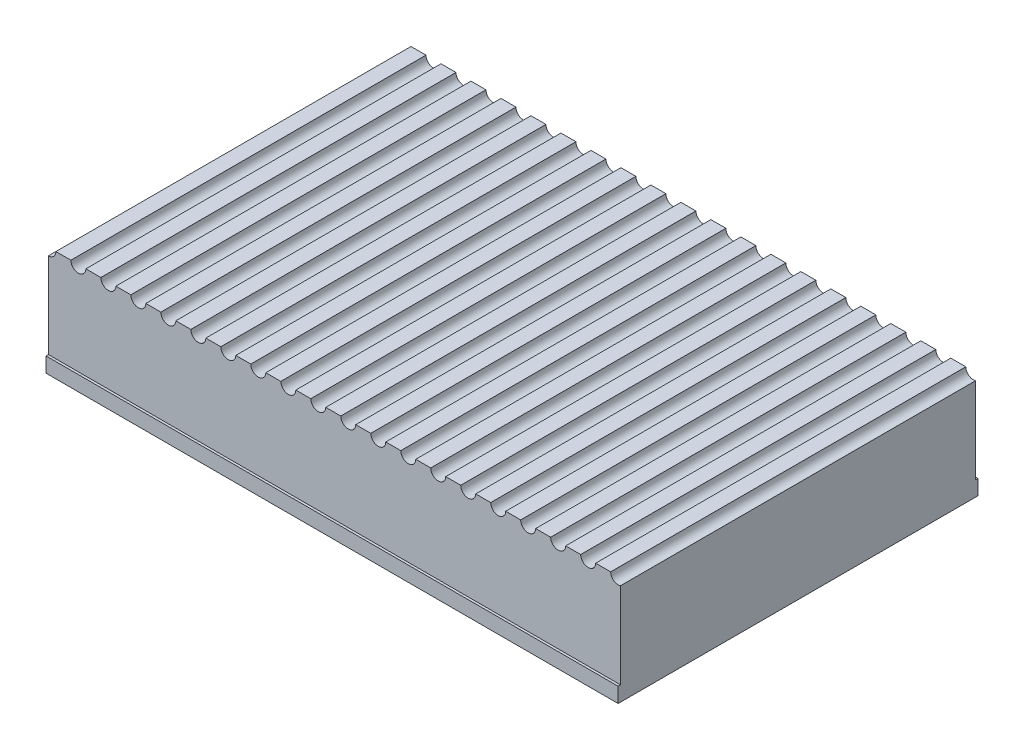
SolidWorks part; units mm, degrees
ref_plane "Front Plane" through (0, 0, 0) normal (0, 0, 1) x (1, 0, 0)
ref_plane "Top Plane" through (0, 0, 0) normal (0, 1, 0) x (1, 0, 0)
ref_plane "Right Plane" through (0, 0, 0) normal (1, 0, 0) x (0, 0, -1)
sketch "Sketch1" plane through (0, 0, 0) normal (0, 1, 0) x (1, 0, 0)
  line L1 (0, 0) -> (-121.1453, 0)
  line L2 (0, 0) -> (0, 76.2)
  line L3 (0, 76.2) -> (-121.1453, 76.2)
  line L4 (-121.1453, 0) -> (-121.1453, 76.2)
  dimension "D1" = 121.1453
  dimension "D2" = 76.2
extrude "Boss-Extrude1" add sketch "Sketch1" along normal blind 3.175
sketch "Sketch3" plane through (0, 3.175, 0) normal (0, 1, 0) x (1, 0, 0)
  line L0 (0, 75.7) -> (-121.1453, 75.7)
  line L1 (-121.1453, 75.7) -> (-121.1453, 0.5)
  line L2 (-121.1453, 0.5) -> (0, 0.5)
  line L3 (0, 0.5) -> (0, 75.7)
  line L6 (0, 0) -> (0, 76.2) construction
  dimension "D1" = 121.1453
extrude "Boss-Extrude4" add sketch "Sketch3" along normal blind 19.685
sketch "Sketch4" plane through (0, 0, -0.5) normal (0, 0, 1) x (1, 0, 0)
  circle A0 centre (-121.1453, 22.86) radius 1.5875
  circle A1 centre (-114.7953, 22.86) radius 1.5875
  circle A2 centre (-108.4453, 22.86) radius 1.5875
  circle A3 centre (-102.0953, 22.86) radius 1.5875
  circle A4 centre (-95.7453, 22.86) radius 1.5875
  circle A5 centre (-89.3953, 22.86) radius 1.5875
  circle A6 centre (-83.0453, 22.86) radius 1.5875
  circle A7 centre (-76.6953, 22.86) radius 1.5875
  circle A8 centre (-70.3453, 22.86) radius 1.5875
  circle A9 centre (-63.9953, 22.86) radius 1.5875
  circle A10 centre (-57.6453, 22.86) radius 1.5875
  circle A11 centre (-51.2953, 22.86) radius 1.5875
  circle A12 centre (-44.9453, 22.86) radius 1.5875
  circle A13 centre (-38.5953, 22.86) radius 1.5875
  circle A14 centre (-32.2453, 22.86) radius 1.5875
  circle A15 centre (-25.8953, 22.86) radius 1.5875
  circle A16 centre (-19.5453, 22.86) radius 1.5875
  circle A17 centre (-13.1953, 22.86) radius 1.5875
  circle A18 centre (-6.8453, 22.86) radius 1.5875
  circle A19 centre (-0.4953, 22.86) radius 1.5875
  circle A20 centre (5.8547, 22.86) radius 1.5875
  dimension "D1" = 3.175
  dimension "D2" = 21
extrude "Cut-Extrude1" cut sketch "Sketch4" against normal through all
